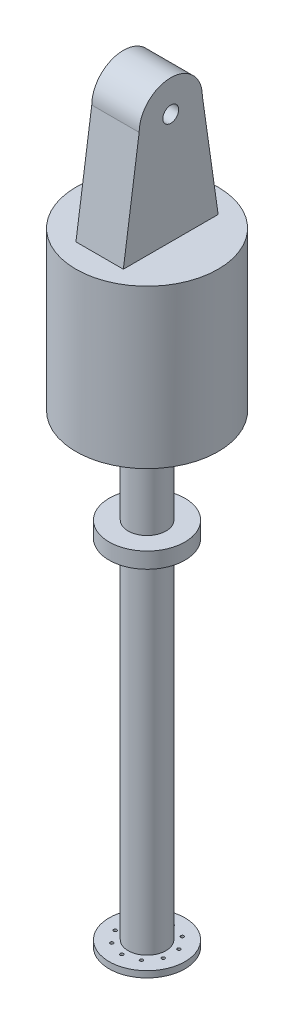
SolidWorks part; units mm, degrees
material "Hexcel AS4C (3000 Filaments)"
ref_plane "Front Plane" through (0, 0, 0) normal (0, 0, 1) x (1, 0, 0)
ref_plane "Top Plane" through (0, 0, 0) normal (0, 1, 0) x (1, 0, 0)
ref_plane "Right Plane" through (0, 0, 0) normal (1, 0, 0) x (0, 0, -1)
sketch "Sketch2" plane through (0, 0, 0) normal (1, 0, 0) x (0, 0, -1)
  line L0 (-10, 64) -> (-15, 29)
  line L1 (-15, 29) -> (15, 29)
  line L2 (15, 29) -> (10, 64)
  circle A0 centre (0, 64) radius 2.5
  arc A1 (10, 64) -> (-10, 64) centre (0, 64) ccw
  dimension "D1" = 5
  dimension "D2" = 20
  dimension "D3" = 64
  dimension "D4" = 35
  dimension "D5" = 30
extrude "Boss-Extrude2" add sketch "Sketch2" along normal blind 15
ref_plane "Plane1" through (0, -10, 0) normal (0, 1, 0) x (1, 0, 0)
sketch "Sketch3" plane through (0, -10, 0) normal (0, 1, 0) x (1, 0, 0)
  circle A2 centre (7.5, 0) radius 22.5
  dimension "D1" = 45
  dimension "D2" = 7.5
extrude "Boss-Extrude16" add sketch "Sketch3" along normal up to surface (39 mm away) up to face at (7.5, 29, 0)
extrude "Boss-Extrude22" add sketch "Sketch3<4>" against normal blind 5
sketch "Sketch3<4>" plane through (0, -10, 0) normal (0, 1, 0) x (1, 0, 0) same geometry as "Sketch3"
sketch "Sketch7" plane through (0, -15, 0) normal (0, -1, 0) x (1, 0, 0)
  circle A0 centre (7.5, 0) radius 22.5
  dimension "D3" = 45
extrude "Boss-Extrude23" add sketch "Sketch7" along normal blind 6
sketch "Sketch8" plane through (0, -21, 0) normal (0, -1, 0) x (1, 0, 0)
  circle A0 centre (7.5, 0) radius 6
  circle A2 centre (7.5, 0) radius 22.5 construction
  dimension "D1" = 12
extrude "Boss-Extrude25" add sketch "Sketch8" along normal blind 30
sketch "Sketch9" plane through (0, -51, 0) normal (0, -1, 0) x (1, 0, 0)
  circle A0 centre (7.5, 0) radius 12
  dimension "D1" = 24
extrude "Boss-Extrude27" add sketch "Sketch9" along normal blind 5
sketch "Sketch10" plane through (0, -56, 0) normal (0, -1, 0) x (1, 0, 0)
  circle A0 centre (7.5, 0) radius 6
  dimension "D1" = 12
extrude "Boss-Extrude28" add sketch "Sketch10" along normal blind 110
sketch "Sketch11" plane through (0, -166, 0) normal (0, -1, 0) x (1, 0, 0)
  line L1 (2.7977, 6.4721) -> (-0.1085, 2.4721) construction
  line L2 (-0.1085, 2.4721) -> (-0.1085, -2.4721) construction
  line L3 (-0.1085, -2.4721) -> (2.7977, -6.4721) construction
  line L4 (2.7977, -6.4721) -> (7.5, -8) construction
  line L5 (7.5, -8) -> (12.2023, -6.4721) construction
  line L6 (12.2023, -6.4721) -> (15.1085, -2.4721) construction
  line L7 (15.1085, -2.4721) -> (15.1085, 2.4721) construction
  line L8 (15.1085, 2.4721) -> (12.2023, 6.4721) construction
  line L9 (12.2023, 6.4721) -> (7.5, 8) construction
  line L10 (7.5, 8) -> (2.7977, 6.4721) construction
  circle A0 centre (7.5, 0) radius 12
  circle A2 centre (7.5, 8) radius 0.5
  circle A3 centre (7.5, 0) radius 8
  circle A4 centre (2.7977, 6.4721) radius 0.5
  circle A5 centre (-0.1085, 2.4721) radius 0.5
  circle A6 centre (2.7977, -6.4721) radius 0.5
  circle A7 centre (-0.1085, -2.4721) radius 0.5
  circle A8 centre (7.5, -8) radius 0.5
  circle A9 centre (12.2023, -6.4721) radius 0.5
  circle A10 centre (15.1085, -2.4721) radius 0.5
  circle A11 centre (15.1085, 2.4721) radius 0.5
  circle A12 centre (12.2023, 6.4721) radius 0.5
  circle A13 centre (7.5, 0) radius 7.6085 construction
  circle M2 centre (7.5, 0) radius 6
  dimension "D1" = 24
  dimension "D2" = 16
  dimension "D3" = 1
extrude "Boss-Extrude30" add sketch "Sketch11" along normal blind 2 contours A0 A12 A3 A11 A10 A9 A8 A6 A7 A5 A4 A2 | A12 A3 A2 A4 A5 A7 A6 A8 A9 A10 A11 M2 | M2 region at (-4.1606, -166, 0) region at (7.5, -166, 7.2739) region at (7.5, -166, 0)
